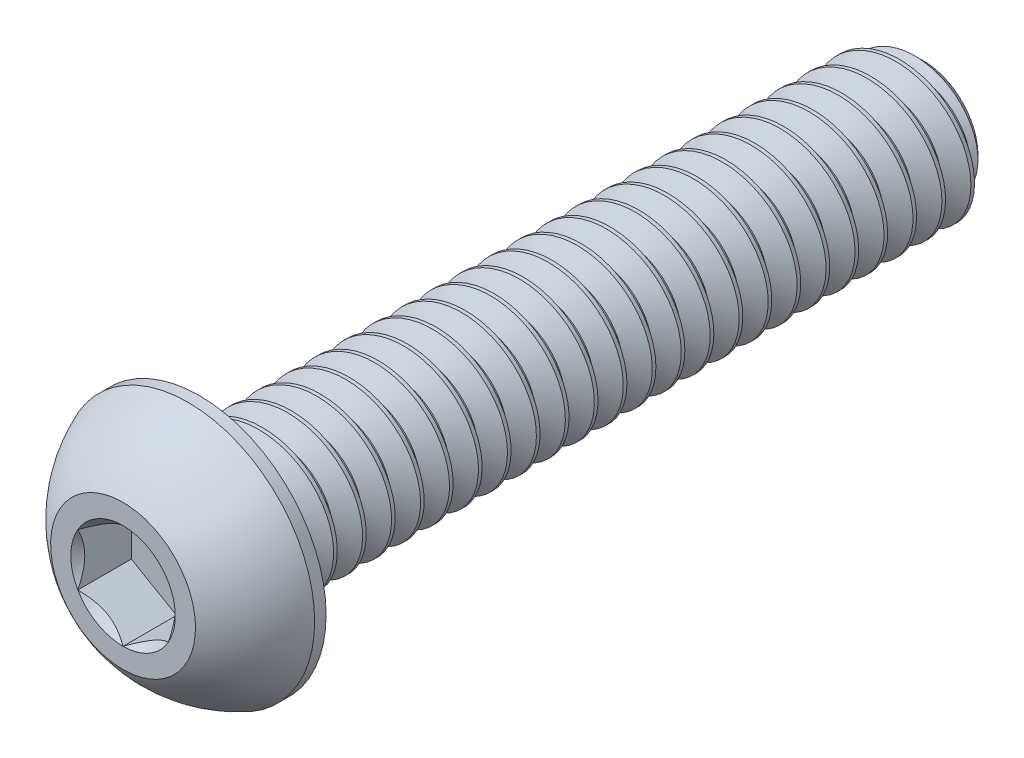
SolidWorks part; units mm, degrees
note: '?' marks a value the reader was unsure of.
ref_plane "Front" through (0, 0, 0) normal (0, 0, 1) x (1, 0, 0)
ref_plane "Top" through (0, 0, 0) normal (0, 1, 0) x (1, 0, 0)
ref_plane "Right" through (0, 0, 0) normal (1, 0, 0) x (0, 0, -1)
sketch "Sketch1" plane through (0, 0, 0) normal (1, 0, 0) x (0, 0, -1)
  line L2 (3.3528, 3.175) -> (35.1028, 3.175) construction
  line L3 (35.1028, 3.175) -> (35.1028, 0) construction
  line L4 (35.1028, 0) -> (3.3528, 0) construction
  line L6 (2.8499, 5.5499) -> (3.3528, 5.5499) construction
  line L7 (35.1028, 3.175) -> (35.1028, -3.175) construction
  line L8 (0, 0) -> (3.3528, 0) construction
  line L9 (3.3528, 5.5499) -> (3.3528, -5.5499) construction
  line L11 (3.3528, 3.175) -> (3.3528, 0) construction
  line L13 (0, 1.9844) -> (0, -1.9844) construction
  line L14 (0, 1.9844) -> (0, 3.175) construction
  arc A3 (0, 3.175) -> (2.8499, 5.5499) centre (5.0603, 0) cw construction
  point P10 (33.1978, -3.175)
  point P16 (11.2903, 0)
  point P19 (27.1653, 0)
  dimension "D1" = 0.5029
  dimension "D2" = 1.905
  dimension "D3" = 7.9375
  dimension "D4" = 7.9375
sketch "Sketch11" plane through (0, 0, 0) normal (1, 0, 0) x (0, 0, -1)
  line L1 (3.3528, 0) -> (35.1028, 0)
  line L4 (3.3528, 3.175) -> (35.1028, 3.175) construction
  line L5 (35.1028, 3.175) -> (35.1028, 0) construction
  line L8 (3.3528, 3.175) -> (35.1028, 3.175)
  line L9 (35.1028, 3.175) -> (35.1028, 0)
  line L10 (3.3528, 3.175) -> (3.3528, 0)
revolve "Revolve1" add sketch "Sketch11" angle 360 about L1
chamfer "Chamfer1" distance 0.7937 angle 45 1 edges at (0, -3.175, -35.1028)
sketch "Sketch7" plane through (0, 0, 0) normal (1, 0, 0) x (0, 0, -1)
  line L6 (2.8499, 5.5499) -> (3.3528, 5.5499) construction
  line L8 (0, 0) -> (3.3528, 0) construction
  line L11 (3.3528, 5.5499) -> (3.3528, -5.5499) construction
  line L12 (2.8499, 5.5499) -> (3.3528, 5.5499)
  line L13 (0, 0) -> (3.3528, 0)
  line L14 (0, 1.9844) -> (0, -1.9844) construction
  line L15 (3.3528, 5.5499) -> (3.3528, 0)
  line L16 (0, 3.175) -> (0, 0)
  arc A2 (2.8499, 5.5499) -> (0, 3.175) centre (5.0603, 0) ccw construction
  arc A3 (2.8499, 5.5499) -> (0, 3.175) centre (5.0603, 0) ccw
revolve "Revolve2" add sketch "Sketch7" angle 360 mid plane about L13
sketch "Sketch5" plane through (0, 0, 0) normal (0, 0, 1) x (1, 0, 0)
  line L1 (1.9844, -1.1457) -> (1.9844, 1.1457)
  line L2 (1.9844, 1.1457) -> (0, 2.2914)
  line L3 (0, 2.2914) -> (-1.9844, 1.1457)
  line L4 (-1.9844, 1.1457) -> (-1.9844, -1.1457)
  line L5 (-1.9844, -1.1457) -> (0, -2.2914)
  line L6 (0, -2.2914) -> (1.9844, -1.1457)
  circle A0 centre (0, 0) radius 1.9844 construction
extrude "Cut-Extrude2" cut sketch "Sketch5" against normal blind 2.347
sketch "Sketch6" plane through (0, 0, 0) normal (0, 0, 1) x (1, 0, 0)
  circle A0 centre (0, 0) radius 2.2914
extrude "Cut-Extrude3" cut sketch "Sketch6" against normal blind 2.347 draft 45
sketch "Sketch3" plane through (0, 0, -35.1028) normal (0, 0, -1) x (-1, 0, 0)
  circle A0 centre (0, 0) radius 3.175
curve "Helix/Spiral1" pitch 1.27 height 33.02 turns 26
sketch "Sketch2" plane through (0, 0, 0) normal (1, 0, 0) x (0, 0, -1)
  line L0 (35.0234, 3.3125) -> (36.2934, 3.3125) construction
  line L1 (36.2934, 3.3125) -> (35.6584, 2.2126) construction
  line L2 (35.6584, 2.2126) -> (35.0234, 3.3125) construction
  line L3 (35.6584, 2.2126) -> (35.6584, 2.3501) construction
  line L4 (35.6584, 2.3501) -> (35.6584, 3.175) construction
  line L5 (35.6584, 3.175) -> (35.6584, 3.3125) construction
  line L6 (35.7378, 2.3501) -> (35.5791, 2.3501) construction
  line L7 (36.2141, 3.175) -> (35.1028, 3.175) construction
  line L8 (36.2537, 3.2437) -> (35.0631, 3.2437) construction
  line L9 (35.0631, 3.2437) -> (36.2537, 3.2437)
  line L10 (36.2537, 3.2437) -> (35.7378, 2.3501)
  line L11 (35.7378, 2.3501) -> (35.5791, 2.3501)
  line L12 (35.5791, 2.3501) -> (35.0631, 3.2437)
  line L13 (35.1028, 3.175) -> (3.3528, 3.175) construction
  line L14 (35.1028, -3.175) -> (35.1028, 3.175)
  line L15 (35.1028, -3.175) -> (35.1028, 3.175) construction
  line L16 (3.3528, -5.5499) -> (3.3528, 5.5499) construction
  point P10 (35.6584, 2.3501)
  point P11 (35.6584, 3.175)
  point P16 (35.6584, 3.2437)
  dimension "D1" = 1.27
  dimension "D2" = 0.1588
sweep "Cut-Sweep1" cut profiles "Sketch2" path "Helix/Spiral1"
sketch "Sketch9" [suppressed] plane through (0, 0, -6.731) normal (0, 0, 1) x (1, 0, 0)
  circle A2 centre (0, 0) radius 6.35
extrude "Boss-Extrude2" [suppressed] add sketch "Sketch9" against normal offset from surface (57.15 mm away) 31.75
ref_axis "Center Axis 1" through (0, 0, -34.309) along (0, 0, 1)?
ref_plane "Contact Plane 1" through (0, 0, -3.3528) normal (0, 0, -1) x (-1, 0, 0)
ref_plane "Contact Plane 2" through (0, 0, -35.1028) normal (0, 0, -1) x (-1, 0, 0)
equation "\"D3@Helix/Spiral1\" = \"Lg@Sketch1\" + \"D4@Helix/Spiral1\""
equation "\"D1@Chamfer1\"=\"D4@Helix/Spiral1\" * .625"
equation "\"D1@Cut-Extrude2\" = \"Head Ht@Sketch1\" * .7"
equation "\"D1@Sketch1\" = \"Head Ht@Sketch1\" * .15"
equation "\"D1@Cut-Extrude3\" = \"D1@Cut-Extrude2\""
equation "\"D2@Sketch1\"=\"D4@Helix/Spiral1\"*1.5"
equation "\"D3@Sketch1\"=\"Lg@Sketch1\"/4"
equation "\"D4@Sketch1\"=\"D3@Sketch1\""
equation "\"D1@Sketch2\"=\"D4@Helix/Spiral1\""
equation "\"D2@Sketch2\"=\"D1@Sketch2\"/8"
